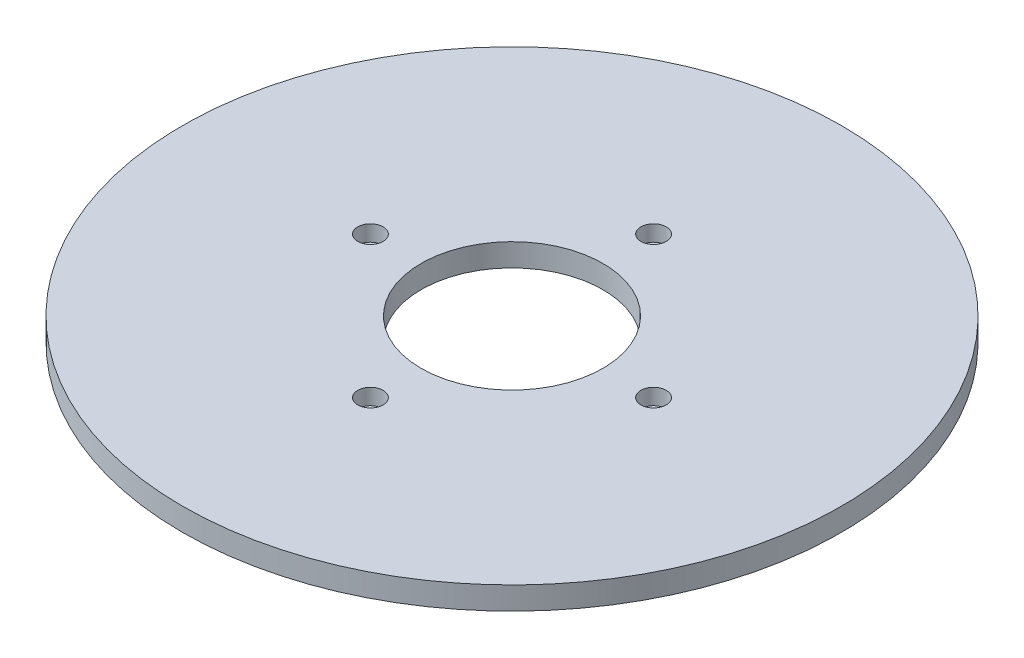
SolidWorks part; units mm, degrees
ref_plane "Front Plane" through (0, 0, 0) normal (0, 0, 1) x (1, 0, 0)
ref_plane "Top Plane" through (0, 0, 0) normal (0, 1, 0) x (1, 0, 0)
ref_plane "Right Plane" through (0, 0, 0) normal (1, 0, 0) x (0, 0, -1)
sketch "Sketch1" plane through (0, 0, 0) normal (0, 1, 0) x (1, 0, 0)
  circle A0 centre (0, 0) radius 72.5
  dimension "FLANGE_OD" = 145
extrude "Boss-Extrude1" add sketch "Sketch1" along normal blind 5
sketch "Sketch2" plane through (0, 0, 0) normal (0, 1, 0) x (1, 0, 0)
  circle A0 centre (0, 0) radius 20
  dimension "BORE_D" = 40
extrude "Cut-Extrude1" cut sketch "Sketch2" along normal through all
sketch "Sketch3" plane through (0, 5, 0) normal (0, 1, 0) x (1, 0, 0)
  circle A0 centre (0, 0) radius 31.145 construction
  circle A1 centre (-31.145, 0) radius 2.7897
  dimension "BOLT_D" = 5.5794
  dimension "BOLT_PCD" = 62.2899
extrude "Cut-Extrude2" cut sketch "Sketch3" against normal blind 3.5139
pattern_circular "CirPattern1" count 4 over 360 about axis through (0, 0, 0) along (0, 1, 0) of "Cut-Extrude2"
